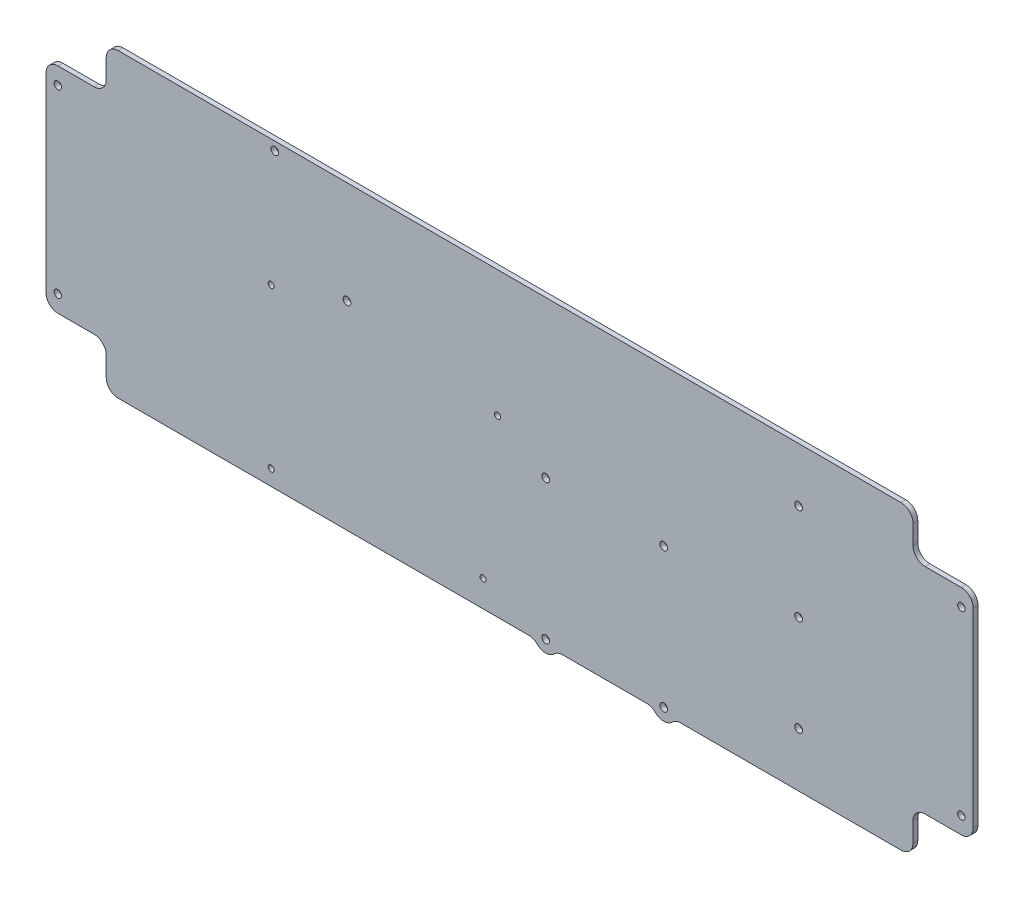
SolidWorks part; units mm, degrees
material "2014 Alloy"
ref_plane "Plan de face" through (0, 0, 0) normal (0, 0, 1) x (1, 0, 0)
ref_plane "Plan de dessus" through (0, 0, 0) normal (0, 1, 0) x (1, 0, 0)
ref_plane "Plan de droite" through (0, 0, 0) normal (1, 0, 0) x (0, 0, -1)
sketch "Sketch1" plane through (0, 0, 0) normal (0, 0, 1) x (1, 0, 0)
  line L1 (-192.5, 62.5) -> (192.5, 62.5)
  line L2 (-192.5, 62.5) -> (-192.5, -62.5)
  line L3 (-192.5, -62.5) -> (192.5, -62.5)
  line L4 (192.5, 62.5) -> (192.5, -62.5)
  line L5 (-192.5, 62.5) -> (192.5, -62.5) construction
  line L6 (-192.5, -62.5) -> (192.5, 62.5) construction
  point P0 (0, 0)
  dimension "D1" = 125
  dimension "D2" = 385
extrude "Boss-Extrude1" add sketch "Sketch1" along normal blind 2
sketch "Sketch2" plane through (0, 0, 2) normal (0, 0, 1) x (1, 0, 0)
  line L1 (-187.6, 37.5) -> (187.6, 37.5) construction
  line L2 (-187.6, 37.5) -> (-187.6, -37.5) construction
  line L3 (-187.6, -37.5) -> (187.6, -37.5) construction
  line L4 (187.6, 37.5) -> (187.6, -37.5) construction
  line L5 (-187.6, 37.5) -> (187.6, -37.5) construction
  line L6 (-187.6, -37.5) -> (187.6, 37.5) construction
  circle A0 centre (-187.6, 37.5) radius 1.55
  circle A1 centre (-187.6, -37.5) radius 1.55
  circle A2 centre (187.6, 37.5) radius 1.55
  circle A3 centre (187.6, -37.5) radius 1.55
  point P0 (0, 0)
  dimension "D1" = 75
  dimension "D2" = 375.2
extrude "Fixing_holes" cut sketch "Sketch2" against normal through all
sketch "Sketch3" plane through (0, 0, 2) normal (0, 0, 1) x (1, 0, 0)
  line L1 (-192.5, 62.5) -> (-167.5, 62.5)
  line L2 (-192.5, 62.5) -> (-192.5, 44.5)
  line L3 (-192.5, 44.5) -> (-167.5, 44.5)
  line L4 (-167.5, 62.5) -> (-167.5, 44.5)
  dimension "D1" = 18
  dimension "D2" = 25
extrude "Cut-Extrude2" cut sketch "Sketch3" against normal through all
mirror "Mirror1" about plane through (0, 0, 0) normal (0, 1, 0) of "Cut-Extrude2"
mirror "Mirror2" about plane through (0, 0, 0) normal (1, 0, 0) of "Mirror1"
sketch "Sketch4" plane through (0, 0, 2) normal (0, 0, 1) x (1, 0, 0)
  line L0 (-99, 10) -> (-5, 10) construction
  line L1 (-99, 10) -> (-99, -56) construction
  circle A0 centre (-99, 10) radius 1.25
  circle A1 centre (-99, -56) radius 1.25
  circle A2 centre (-5, 10) radius 1.25
  circle A3 centre (-11, -51.5) radius 1.25
  dimension "D4" = 66
  dimension "D5" = 94
  dimension "D7" = 61.5
  dimension "D8" = 6
  dimension "D1" = 5
  dimension "D2" = 10
extrude "Cave_board_holes" cut sketch "Sketch4" against normal through all
sketch "Sketch5" plane through (0, 0, 2) normal (0, 0, 1) x (1, 0, 0)
  line L1 (15, -2.4) -> (64, -2.4) construction
  line L2 (15, -2.4) -> (15, -60.4) construction
  line L3 (15, -60.4) -> (64, -60.4) construction
  line L4 (64, -2.4) -> (64, -60.4) construction
  circle A0 centre (15, -2.4) radius 1.6
  circle A1 centre (15, -60.4) radius 1.6
  circle A2 centre (64, -2.4) radius 1.6
  circle A3 centre (64, -60.4) radius 1.6
  dimension "D1" = 58
  dimension "D2" = 49
  dimension "D3" = 15
  dimension "D4" = 2.4
extrude "RPi_holes" cut sketch "Sketch5" against normal through all
sketch "Sketch6" plane through (0, 0, 2) normal (0, 0, 1) x (1, 0, 0)
  line L1 (-97.5, 59) -> (-67.5, 59) construction
  line L2 (-97.5, 59) -> (-97.5, 20) construction
  line L3 (-97.5, 20) -> (-67.5, 20) construction
  line L4 (-67.5, 59) -> (-67.5, 20) construction
  circle A0 centre (-97.5, 59) radius 1.6
  circle A3 centre (-67.5, 20) radius 1.6
  dimension "D1" = 39
  dimension "D2" = 30
  dimension "D3" = 67.5
  dimension "D4" = 20
extrude "buzzer_holes" cut sketch "Sketch6" against normal through all
sketch "Sketch7" plane through (0, 0, 2) normal (0, 0, 1) x (1, 0, 0)
  line L0 (0, 0) -> (178.5314, 0) construction
  circle A0 centre (120, 0) radius 1.6
  circle A1 centre (120, 40) radius 1.6
  circle A2 centre (120, -40) radius 1.6
  dimension "D4" = 120
  dimension "D5" = 40
extrude "relays_holes" cut sketch "Sketch7" against normal through all
sketch "Sketch8" plane through (0, 0, 2) normal (0, 0, 1) x (1, 0, 0)
  line L0 (-167.5, -62.5) -> (167.5, -62.5) construction
  line L2 (10.4624, -62.5) -> (19.5376, -62.5)
  line L3 (59.4624, -62.5) -> (68.5376, -62.5)
  arc A0 (10.4624, -62.5) -> (19.5376, -62.5) centre (15, -60.4) ccw
  arc A1 (59.4624, -62.5) -> (68.5376, -62.5) centre (64, -60.4) ccw
  dimension "D1" = 10
  dimension "D2" = 10
extrude "Boss-Extrude2" add sketch "Sketch8" against normal up to surface (2 mm away) up to face at (121.6, -40, 0)
fillet "Fillet1" radius 5 16 edges at (68.5376, -62.5, 1) (59.4624, -62.5, 1) (19.5376, -62.5, 1) (10.4624, -62.5, 1) (-192.5, 44.5, 1) (-167.5, 44.5, 1) (-167.5, 62.5, 1) (-167.5, -62.5, 1) (-167.5, -44.5, 1) (-192.5, -44.5, 1) (167.5, -62.5, 1) (167.5, -44.5, 1) (192.5, -44.5, 1) (192.5, 44.5, 1) (167.5, 44.5, 1) (167.5, 62.5, 1)
